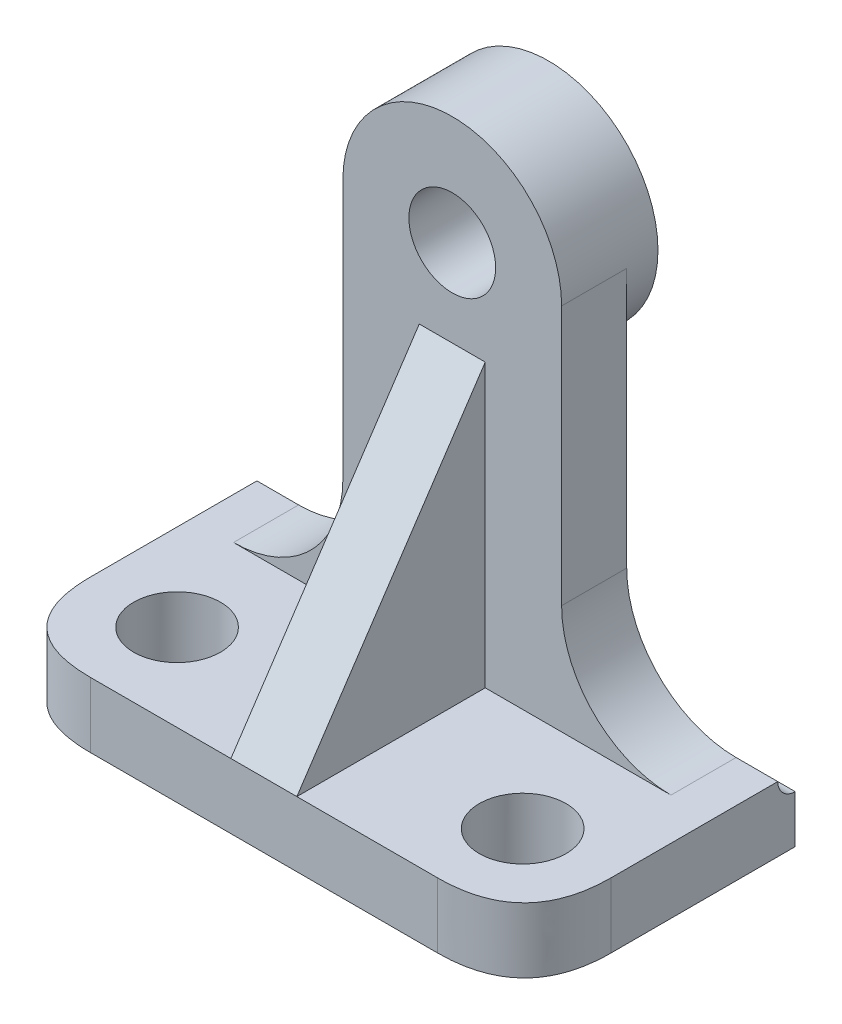
SolidWorks part; units mm, degrees
material "Gray Cast Iron"
ref_plane "Front" through (0, 0, 0) normal (0, 0, 1) x (1, 0, 0)
ref_plane "Top" through (0, 0, 0) normal (0, 1, 0) x (1, 0, 0)
ref_plane "Right" through (0, 0, 0) normal (1, 0, 0) x (0, 0, -1)
sketch "Sketch1" plane through (0, 0, 0) normal (0, 1, 0) x (1, 0, 0)
  line L1 (-38.1, -19.812) -> (38.1, -19.812)
  line L2 (-38.1, -19.812) -> (-38.1, 19.812)
  line L3 (-38.1, 19.812) -> (38.1, 19.812)
  line L4 (38.1, -19.812) -> (38.1, 19.812)
  line L5 (-38.1, -19.812) -> (38.1, 19.812) construction
  line L6 (-38.1, 19.812) -> (38.1, -19.812) construction
  point P0 (0, 0)
  dimension "D1" = 76.2
  dimension "D2" = 39.624
extrude "Boss-Extrude1" add sketch "Sketch1" against normal blind 9.525
sketch "Sketch2" plane through (38.1, 0, 0) normal (1, 0, 0) x (0, 0, -1)
  line L0 (17.272, 0) -> (19.812, 0)
  line L1 (19.812, 0) -> (19.812, -2.54)
  arc A0 (17.272, 0) -> (19.812, -2.54) centre (19.812, 0) ccw
  dimension "D1" = 5.08
extrude "Cut-Extrude1" cut sketch "Sketch2" against normal through all
fillet "Fillet1" radius 12.7 2 edges at (-38.1, -4.7625, 19.812) (38.1, -4.7625, 19.812) conic rho 0.5
ref_plane "Plane7" through (0, 0, -17.272) normal (0, 0, 1) x (1, 0, 0)
sketch "Sketch12" plane through (0, 0, -17.272) normal (0, 0, 1) x (1, 0, 0)
  line L0 (0, 0) -> (0, 53.975) construction
  line L1 (-25.4, -9.525) -> (25.4, -9.525) construction
  line L2 (-16.002, 53.975) -> (-16.002, 16.002)
  line L4 (16.002, 53.975) -> (16.002, 16.002)
  line L5 (-32.004, 0) -> (32.004, 0)
  circle A0 centre (0, 53.975) radius 6.35
  arc A1 (16.002, 53.975) -> (-16.002, 53.975) centre (0, 53.975) ccw
  arc A4 (16.002, 16.002) -> (32.004, 0) centre (32.004, 16.002) ccw
  arc A5 (-32.004, 0) -> (-16.002, 16.002) centre (-32.004, 16.002) ccw
  dimension "D2" = 12.7
  dimension "D3" = 16.002
  dimension "D1" = 63.5
extrude "Boss-Extrude4" add sketch "Sketch12" along normal blind 9.525
sketch "Sketch13" plane through (0, 0, -7.747) normal (0, 0, 1) x (1, 0, 0)
  circle A0 centre (0, 53.975) radius 16.002
  dimension "D1" = 32.004
extrude "Boss-Extrude5" add sketch "Sketch13" against normal blind 14.097
sketch "Sketch14" plane through (0, 0, -7.747) normal (0, 0, 1) x (1, 0, 0)
  circle A0 centre (0, 53.975) radius 6.35
  dimension "D1" = 12.7
extrude "Cut-Extrude4" cut sketch "Sketch14" against normal through all
ref_plane "Plane8" through (0, 0, 0) normal (1, 0, 0) x (0, 0, -1)
sketch "Sketch15" plane through (0, 0, 0) normal (1, 0, 0) x (0, 0, -1)
  line L0 (7.747, 0) -> (7.747, 41.275)
  line L1 (7.747, 16.002) -> (7.747, 53.975) construction
  line L2 (-7.112, -9.525) -> (19.812, -9.525) construction
  line L3 (7.747, 41.275) -> (-19.812, 0)
  line L4 (-19.812, 0) -> (7.747, 0)
  dimension "D1" = 50.8
extrude "Boss-Extrude6" add sketch "Sketch15" along normal mid plane 9.652
hole_wizard "3/8 (0.5) Diameter Hole1" positions "3DSketch2" profile "Sketch16" hole size "3/8" standard "ANSI Inch" end condition through all
sketch3d "3DSketch2"
  line L0 (-25.4, 0, 19.812) -> (-4.826, 0, 19.812) construction
  line L1 (-38.1, 0, -17.272) -> (-38.1, 0, 7.112) construction
  point P0 (-25.4, 0, 7.112)
  point P2 (25.3994, 0, 7.3505)
  dimension "D1" = 50.8
  dimension "D2" = 12.7
  dimension "D3" = 12.7
sketch "Sketch16" plane through (-25.4, 0, 7.112) normal (1, 0, 0) x (0, 0, 1)
  line L0 (0, 0) -> (0, 9.5885)
  line L1 (0, 9.5885) -> (6.35, 9.5885)
  line L2 (6.35, 9.5885) -> (6.35, 0)
  line L5 (6.35, 0) -> (0, 0)
  line L11 (0, -6.35) -> (0, 107.95) construction
  dimension "Thru Hole Dia." = 12.7
  dimension "Thru Hole Depth" = 9.5885
